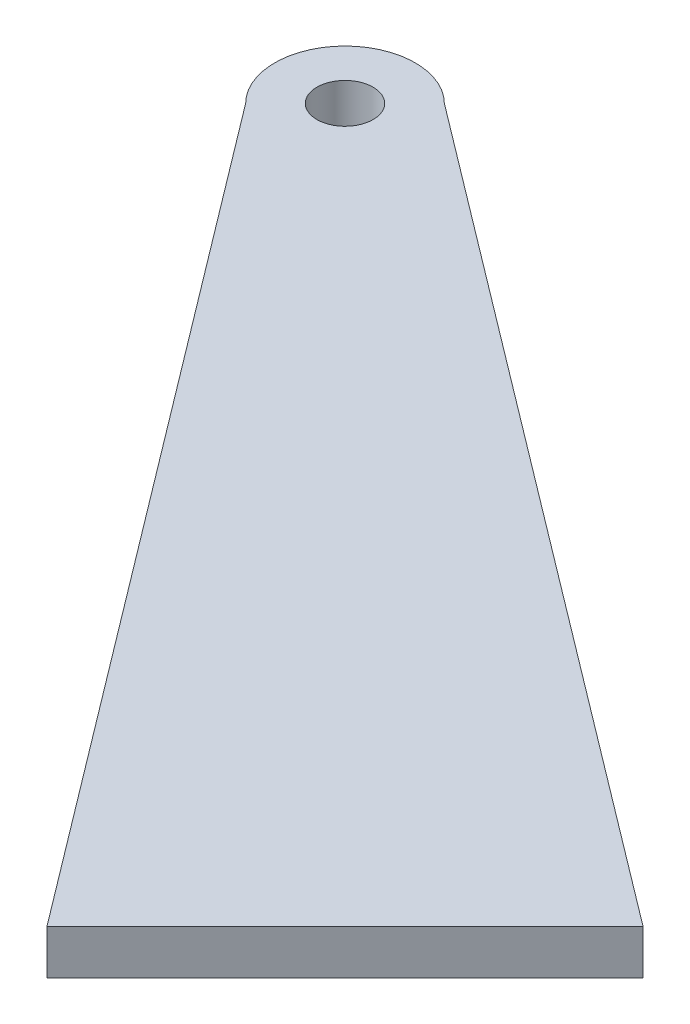
SolidWorks part; units mm, degrees
ref_plane "Front Plane" through (0, 0, 0) normal (0, 0, 1) x (1, 0, 0)
ref_plane "Top Plane" through (0, 0, 0) normal (0, 1, 0) x (1, 0, 0)
ref_plane "Right Plane" through (0, 0, 0) normal (1, 0, 0) x (0, 0, -1)
sketch "Sketch1" plane through (0, 0, 0) normal (0, 1, 0) x (1, 0, 0)
  line L0 (0, -99) -> (0, 99) construction
  line L1 (-99, 0) -> (99, 0) construction
  line L2 (-98.7155, -7.5) -> (98.7155, -7.5) construction
  line L3 (7.5, -98.7155) -> (7.5, 98.7155) construction
  line L4 (-98.7155, 7.5) -> (98.7155, 7.5) construction
  line L5 (-7.5, -98.7155) -> (-7.5, 98.7155) construction
  line L6 (-7.5, -99) -> (-7.5, 99) construction
  line L7 (7.5, -99) -> (7.5, 99) construction
  line L8 (-99, -7.5) -> (99, -7.5) construction
  line L9 (-99, 7.5) -> (99, 7.5) construction
  line L10 (-88.3883, -88.3883) -> (17.6777, -194.4544) construction
  line L11 (17.6777, -194.4544) -> (194.4544, -17.6777) construction
  line L12 (194.4544, -17.6777) -> (88.3883, 88.3883) construction
  line L13 (0, 0) -> (33755.9757, 33755.9757) construction
  line L14 (-88.3883, -88.3883) -> (-70.0036, -70.0036) construction
  line L15 (88.3883, 88.3883) -> (70.0036, 70.0036) construction
  line L16 (106.066, -106.066) -> (70.0036, -70.0036) construction
  line L23 (110.6622, -101.4698) -> (74.4487, -65.2563) construction
  line L24 (88.3883, 79.196) -> (74.4487, 65.2563) construction
  line L25 (185.262, -17.6777) -> (88.3883, 79.196) construction
  line L26 (17.6777, -185.262) -> (185.262, -17.6777) construction
  line L27 (-79.196, -88.3883) -> (17.6777, -185.262) construction
  line L28 (-79.196, -88.3883) -> (-65.2563, -74.4487) construction
  line L30 (-79.196, -88.3883) -> (-65.4074, -74.5998) construction
  line L32 (88.3883, 79.196) -> (74.5998, 65.4074) construction
  line L34 (110.6622, -101.4698) -> (74.5998, -65.4074) construction
  line L35 (0, 0) -> (101.4698, -101.4698) construction
  line L36 (-7.0711, -7.0711) -> (80.2566, -122.683)
  line L37 (7.0711, 7.0711) -> (122.683, -80.2566)
  line L38 (-7.0711, -7.0711) -> (7.0711, 7.0711) construction
  line L39 (80.2566, -122.683) -> (122.683, -80.2566)
  circle A0 centre (0, 0) radius 100 construction
  circle A1 centre (0, 0) radius 99 construction
  circle A2 centre (0, 0) radius 84 construction
  arc A3 (-7.0711, -7.0711) -> (7.0711, 7.0711) centre (0, 0) cw
  point P0 (101.4698, -101.4698)
  point P7 (0, 0)
  point P11 (0, 0)
  dimension "D1" = 200
  dimension "D2" = 1
  dimension "D3" = 15
  dimension "D6" = 25
  dimension "D7" = 25
  dimension "D8" = 50
  dimension "D11" = 10
  dimension "D9" = 7.5
  dimension "D10" = 45
  dimension "D15" = 60
  dimension "D12" = 143.5
  dimension "D4" = 7.5
  dimension "D5" = 7.5
extrude "Boss-Extrude1" add sketch "Sketch1" along normal mid plane 6.35 contours A2 L2 A1 L5 | A2 L4 A1 L2 | A2 L5 A1 L4 | A2 L3 A1 L5 | A2 L4 A1 L3 | A2 L2 A1 L4 | A2 L3 A1 L2 | A2 L5 A1 L3 | L5 A2 L3 L2 | L4 A2 L2 L5 | L3 A2 L5 L4 | L2 A2 L4 L3 | L5 L2 L3 L4 | A1 L28 L27 L26 L25 L24 | A1 L23 | A3 L36 L39 L37 region at (57.5341, 0, 57.5341)
hole_wizard "Ø8.0 (8) Diameter Hole1" positions "Sketch5" profile "Sketch6" hole size "Ø8.0" standard "ANSI Metric" end condition up to next
sketch "Sketch5" plane through (0, 3.175, 0) normal (0, 1, 0) x (1, 0, 0)
  point P0 (0, 0)
sketch "Sketch6" plane through (0, 3.175, 0) normal (1, 0, 0) x (0, 0, 1)
  line L0 (0, 0) -> (0, 6.35)
  line L1 (0, 6.35) -> (4, 6.35)
  line L2 (4, 6.35) -> (4, 0)
  line L5 (4, 0) -> (0, 0)
  line L11 (0, -6.35) -> (0, 107.95) construction
  dimension "Thru Hole Dia." = 8
  dimension "Thru Hole Depth" = 6.35
